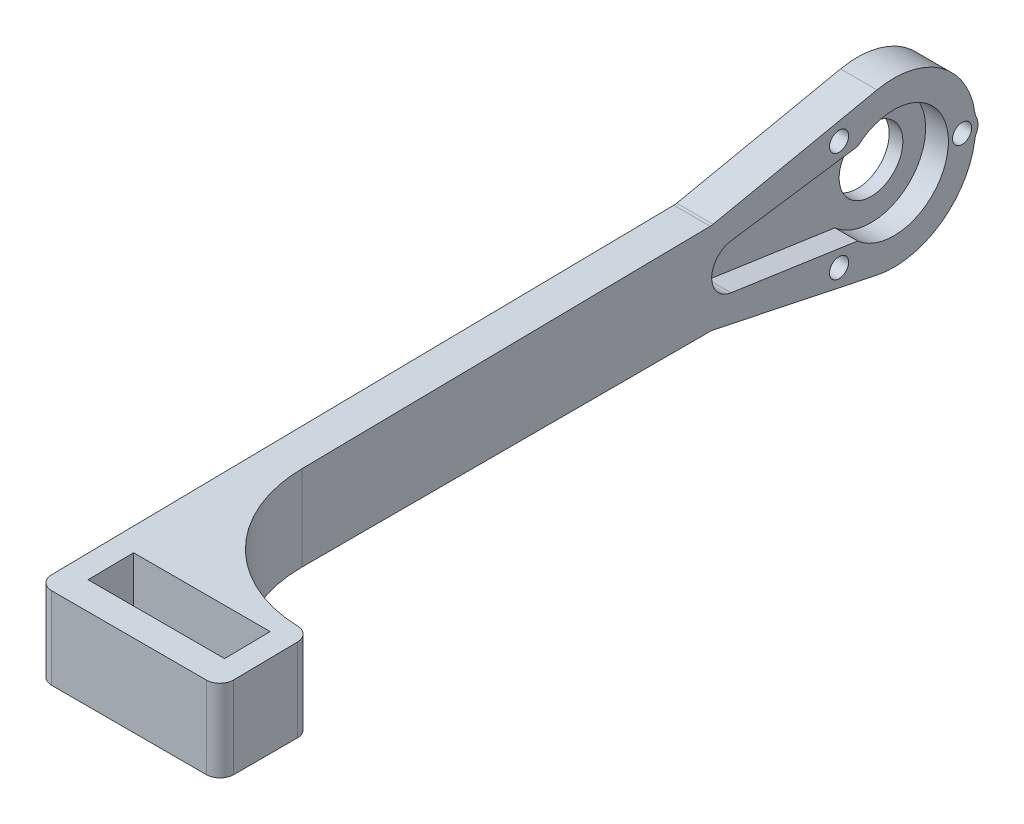
SolidWorks part; units mm, degrees
ref_plane "Plan de face" through (0, 0, 0) normal (0, 0, 1) x (1, 0, 0)
ref_plane "Plan de dessus" through (0, 0, 0) normal (0, 1, 0) x (1, 0, 0)
ref_plane "Plan de droite" through (0, 0, 0) normal (1, 0, 0) x (0, 0, -1)
sketch "Esquisse1" plane through (0, 0, 0) normal (1, 0, 0) x (0, 0, -1)
  line L0 (-47.7273, 0) -> (57.7273, 0) construction
  line L1 (-30, 5) -> (-30, -5)
  line L4 (0, 18.828) -> (0, -23.0645) construction
  line L7 (-30, 5) -> (30, 5)
  line L8 (-30, -5) -> (30, -5)
  line L9 (30, 12.9505) -> (30, -16.4973) construction
  line L10 (48.1521, 8.8082) -> (48.1521, -18.9143) construction
  line L11 (30, 5) -> (48.1521, 8.8082)
  line L12 (30, -5) -> (48.1521, -8.8082)
  line L13 (50, 0) -> (50, 9) construction
  circle A2 centre (-40, 0) radius 11.1803 construction
  arc A5 (48.1521, 8.8082) -> (48.1521, -8.8082) centre (50, 0) cw construction
  arc A8 (48.1521, -8.8082) -> (58.9458, -0.9859) centre (50, 0) ccw
  arc A9 (48.1521, 8.8082) -> (58.9458, 0.9859) centre (50, 0) cw
  circle A10 centre (57.5, 0) radius 1.75 construction
  arc A11 (58.9458, 0.9859) -> (58.9458, -0.9859) centre (57.5, 0) cw
  point P20 (0, -5)
  point P22 (0, 5)
  dimension "D3" = 10
  dimension "D4" = 9
  dimension "D6" = 3.5
  dimension "D5" = 7.5
  dimension "D7" = 40
  dimension "D1" = 80
  dimension "D2" = 90
  dimension "D8" = 20
extrude "Boss.-Extru.1" add sketch "Esquisse1" along normal blind 4 contours L1 | L1 L8 L12 A8 A11 A9 L11 L7 region at (0, 0, -18.2864)
sketch "Esquisse2" plane through (4, 0, 0) normal (1, 0, 0) x (0, 0, -1)
  line L2 (48.1521, 8.8082) -> (30, 5)
  line L8 (30, 5) -> (-30, 5)
  line L9 (30, 5) -> (-30, 5)
  line L10 (-30, -5) -> (30, -5)
  line L11 (-30, -5) -> (30, -5)
  line L14 (48.1521, 8.8082) -> (30, 5)
  line L16 (30, -5) -> (48.1521, -8.8082)
  line L17 (30, -5) -> (48.1521, -8.8082)
  line L19 (-30, 5) -> (-30, -5)
  line L20 (-30, 5) -> (-30, -5)
  arc A2 (58.9458, 0.9859) -> (48.1521, 8.8082) centre (50, 0) ccw
  circle A6 centre (50, 0) radius 3.5
  arc A15 (58.9458, -0.9859) -> (58.9458, 0.9859) centre (57.5, 0) ccw
  arc A17 (58.9458, 0.9859) -> (48.1521, 8.8082) centre (50, 0) ccw
  arc A18 (48.1521, -8.8082) -> (58.9458, -0.9859) centre (50, 0) ccw
  arc A19 (48.1521, -8.8082) -> (58.9458, -0.9859) centre (50, 0) ccw
  arc A21 (58.9458, -0.9859) -> (58.9458, 0.9859) centre (57.5, 0) ccw
  dimension "D3" = 7
  dimension "D1" = 0
extrude "Enlèv. mat.-Extru.1" cut sketch "Esquisse2" against normal blind 10 contours A6
sketch "Esquisse3" plane through (4, 0, 0) normal (1, 0, 0) x (0, 0, -1)
  line L0 (0, 0) -> (74.7488, 0) construction
  line L1 (38.1014, 11.1997) -> (38.1014, -12.7742) construction
  line L2 (48.1521, 8.8082) -> (30, 5)
  line L6 (23.0641, 4.5) -> (53.2637, 4.5) construction
  line L7 (0, 17.2639) -> (0, -16.0675) construction
  line L8 (30.5083, 6.6344) -> (30.5083, -6.2819) construction
  line L9 (32.1392, 2.4738) -> (46.0314, 4.5)
  line L10 (32.1392, -2.4738) -> (46.0314, -4.5)
  line L15 (30, 5) -> (-30, 5)
  line L16 (30, 5) -> (-30, 5)
  line L17 (-30, -5) -> (30, -5)
  line L18 (-30, -5) -> (30, -5)
  line L21 (48.1521, 8.8082) -> (30, 5)
  line L23 (30, -5) -> (48.1521, -8.8082)
  line L24 (30, -5) -> (48.1521, -8.8082)
  line L26 (-30, 5) -> (-30, -5)
  line L27 (-30, 5) -> (-30, -5)
  circle A0 centre (50, 0) radius 6 construction
  circle A1 centre (32.5, 0) radius 2.5 construction
  arc A2 (58.9458, 0.9859) -> (48.1521, 8.8082) centre (50, 0) ccw
  arc A6 (32.1392, -2.4738) -> (32.1392, 2.4738) centre (32.5, 0) cw
  arc A7 (46.0314, -4.5) -> (46.0314, 4.5) centre (50, 0) ccw
  arc A16 (58.9458, -0.9859) -> (58.9458, 0.9859) centre (57.5, 0) ccw
  arc A18 (58.9458, 0.9859) -> (48.1521, 8.8082) centre (50, 0) ccw
  arc A19 (48.1521, -8.8082) -> (58.9458, -0.9859) centre (50, 0) ccw
  arc A20 (48.1521, -8.8082) -> (58.9458, -0.9859) centre (50, 0) ccw
  arc A22 (58.9458, -0.9859) -> (58.9458, 0.9859) centre (57.5, 0) ccw
  dimension "D2" = 12
  dimension "D4" = 17.5
  dimension "D5" = 5
  dimension "D3" = 4.5
  dimension "D1" = 0
extrude "Enlèv. mat.-Extru.2" cut sketch "Esquisse3" against normal blind 2.5 contours A7 L9 A6 L10
sketch "Esquisse5" plane through (4, 0, 0) normal (1, 0, 0) x (0, 0, -1)
  line L0 (0, 16.8077) -> (0, -27.9422) construction
  line L1 (-64.0496, 0) -> (62.7771, 0) construction
  line L2 (32.1392, -2.4738) -> (46.0314, -4.5)
  line L3 (46.0314, 4.5) -> (32.1392, 2.4738)
  line L4 (32.1392, -2.4738) -> (46.0314, -4.5)
  line L5 (46.0314, 4.5) -> (32.1392, 2.4738)
  line L6 (50, 0) -> (34.0152, 15.9848) construction
  line L8 (48.1521, 8.8082) -> (30, 5)
  line L9 (30, 5) -> (-30, 5)
  line L10 (-30, -5) -> (30, -5)
  line L13 (30, 5) -> (-30, 5)
  line L14 (-30, -5) -> (30, -5)
  line L18 (48.1521, 8.8082) -> (30, 5)
  line L20 (30, -5) -> (48.1521, -8.8082)
  line L21 (30, -5) -> (48.1521, -8.8082)
  line L24 (-30, 5) -> (-30, -5)
  line L25 (-30, 5) -> (-30, -5)
  arc A2 (46.0314, -4.5) -> (46.0314, 4.5) centre (50, 0) ccw
  arc A3 (32.1392, 2.4738) -> (32.1392, -2.4738) centre (32.5, 0) ccw
  arc A4 (46.0314, -4.5) -> (46.0314, 4.5) centre (50, 0) ccw
  arc A5 (32.1392, 2.4738) -> (32.1392, -2.4738) centre (32.5, 0) ccw
  arc A6 (58.9458, 0.9859) -> (48.1521, 8.8082) centre (50, 0) ccw
  circle A10 centre (50, 0) radius 8.5 construction
  circle A11 centre (43.9896, 6.0104) radius 1.05
  circle A12 centre (43.9896, -6.0104) radius 1.05
  circle A13 centre (57.5, 0) radius 1.05
  arc A17 (58.9458, -0.9859) -> (58.9458, 0.9859) centre (57.5, 0) ccw
  arc A22 (58.9458, 0.9859) -> (48.1521, 8.8082) centre (50, 0) ccw
  arc A23 (48.1521, -8.8082) -> (58.9458, -0.9859) centre (50, 0) ccw
  arc A24 (48.1521, -8.8082) -> (58.9458, -0.9859) centre (50, 0) ccw
  arc A26 (58.9458, -0.9859) -> (58.9458, 0.9859) centre (57.5, 0) ccw
  dimension "D3" = 2.1
  dimension "D4" = 17
  dimension "D5" = 45
  dimension "D1" = 0
  dimension "D2" = 0
extrude "Enlèv. mat.-Extru.3" cut sketch "Esquisse5" against normal through all contours A11 | A12 | A13
sketch "Esquisse6" plane through (0, 0, 30) normal (0, 0, 1) x (1, 0, 0)
  line L0 (2, 5) -> (2, -5) construction
  line L1 (0, 5) -> (0, -5)
  line L4 (0, 5) -> (0, -5)
  line L5 (0, -5) -> (4, -5)
  line L6 (4, -5) -> (4, 5)
  line L7 (4, 5) -> (0, 5)
  line L9 (0, -5) -> (4, -5)
  line L10 (4, -5) -> (4, 5)
  line L11 (4, 5) -> (0, 5)
  line L12 (20, -5) -> (4, -5)
  line L13 (20, 5) -> (20, -5)
  line L14 (4, 5) -> (20, 5)
  point P3 (20, 0)
  point P7 (20, 8.3224)
  line M9 (0, 5) -> (0, -5)
  line M10 (0, -5) -> (4, -5)
  line M11 (4, -5) -> (4, 5)
  line M12 (4, 5) -> (0, 5)
  dimension "D2" = 18
  dimension "D1" = 0
extrude "Boss.-Extru.2" add sketch "Esquisse6" along normal blind 10 contours L14 L12 L13 M11 | L0 L9 M12 M11 | L0 L11 M9 M10 | M9 region at (3, 0, 30) region at (1, 0, 30) region at (12, 0, 30)
sketch "Esquisse7" plane through (0, 5, 0) normal (0, 1, 0) x (1, 0, 0)
  line L0 (10, -40) -> (10, -30) construction
  line L1 (17.5, -37) -> (2.5, -37)
  line L2 (17.5, -37) -> (17.5, -32)
  line L3 (17.5, -32) -> (2.5, -32)
  line L4 (2.5, -37) -> (2.5, -32)
  line L5 (17.5, -37) -> (2.5, -32) construction
  line L6 (17.5, -32) -> (2.5, -37) construction
  line L8 (4, -30) -> (4, 30)
  line L9 (4, 30) -> (0, 30)
  line L10 (0, 30) -> (0, -40)
  line L11 (0, -40) -> (20, -40)
  line L12 (0, -40) -> (20, -40)
  line L13 (20, -40) -> (20, -30)
  line L14 (20, -40) -> (20, -30)
  line L15 (20, -30) -> (4, -30)
  line L16 (4, -30) -> (4, 30)
  line L18 (0, 30) -> (0, -40)
  line L29 (20, -30) -> (4, -30)
  line L32 (4, 30) -> (0, 30)
  point P2 (10, -34.5)
  dimension "D2" = 15
  dimension "D3" = 5
  dimension "D4" = 2
  dimension "D1" = 0
extrude "Enlèv. mat.-Extru.4" cut sketch "Esquisse7" against normal blind 10 contours L2 L1 L4 L3
fillet "Congé2" radius 1.5 7 edges at (2, 0.9859, -58.9458) (2, -0.9859, -58.9458) (2, 5, -30) (2, -5, -30) (20, 0, 30) (20, 0, 40) (0, 0, 40)
fillet "Congé3" radius 15 1 edges at (4, 0, 30)
sketch "Esquisse8" plane through (20, 0, 0) normal (1, 0, 0) x (0, 0, -1)
  line L0 (-40, 5) -> (-40, 4)
  line L1 (-40, 4) -> (29.8443, 5)
  line L2 (29.8443, 5) -> (-39.25, 5)
  line L3 (-38.5, 5) -> (-40, 5) construction
  line L4 (-38.5, 5) -> (-40, 5)
  line L5 (-40, 5) -> (-40, -5)
  line L6 (-40, -5) -> (-38.5, -5)
  line L7 (-38.5, -5) -> (-38.5, 5)
  line L8 (-38.5, 5) -> (-40, 5) construction
  line L9 (-40, 5) -> (-40, -5) construction
  line L10 (-40, -5) -> (-38.5, -5) construction
  line L11 (-38.5, -5) -> (-38.5, 5) construction
  line L12 (-38.5, -5) -> (-31.5, -5)
  line L13 (-31.5, -5) -> (-31.5, 5)
  line L14 (-31.5, 5) -> (-38.5, 5)
  line L15 (-38.5, 5) -> (-38.5, -5)
  line L16 (-38.5, -5) -> (-31.5, -5) construction
  line L17 (-31.5, -5) -> (-31.5, 5) construction
  line L18 (-31.5, 5) -> (-38.5, 5) construction
  line L19 (-38.5, 5) -> (-38.5, -5) construction
  line L20 (-31.5, -5) -> (-30.0007, -5)
  line L21 (-30.0007, -5) -> (-30.0007, 5)
  line L22 (-30.0007, 5) -> (-31.5, 5)
  line L23 (-31.5, 5) -> (-31.5, -5)
  line L24 (-31.5, -5) -> (-30.0007, -5) construction
  line L25 (-30.0007, -5) -> (-30.0007, 5) construction
  line L26 (-30.0007, 5) -> (-31.5, 5) construction
  line L27 (-31.5, 5) -> (-31.5, -5) construction
  line L28 (-15.0076, 5) -> (-30.0007, 5)
  line L29 (-30.0007, 5) -> (-30.0007, -5)
  line L30 (-30.0007, -5) -> (-15.0076, -5)
  line L31 (-15.0076, -5) -> (-15.0076, 5)
  line L32 (-15.0076, 5) -> (-30.0007, 5) construction
  line L33 (-30.0007, 5) -> (-30.0007, -5) construction
  line L34 (-30.0007, -5) -> (-15.0076, -5) construction
  line L35 (-15.0076, -5) -> (-15.0076, 5) construction
  line L36 (-39.25, 5) -> (-40, 5)
  line L37 (29.8443, 5) -> (-15.0076, 5)
  line L38 (-15.0076, 5) -> (-15.0076, -5)
  line L39 (-15.0076, -5) -> (29.8443, -5)
  line L40 (30.1523, -5.032) -> (48.1521, -8.8082)
  line L41 (48.1521, 8.8082) -> (30.1523, 5.032)
  line L42 (29.8443, 5) -> (-15.0076, 5) construction
  line L43 (-15.0076, 5) -> (-15.0076, -5) construction
  line L44 (-15.0076, -5) -> (29.8443, -5) construction
  line L45 (30.1523, -5.032) -> (48.1521, -8.8082) construction
  line L46 (48.1521, 8.8082) -> (30.1523, 5.032) construction
  line L47 (11, 0) -> (-11, 0) construction
  line L48 (29.8443, -5) -> (-39.25, -5)
  line L49 (-40, -4) -> (29.8443, -5)
  line L50 (-40, -5) -> (-40, -4)
  line L51 (-39.25, -5) -> (-40, -5)
  arc A7 (30.1523, -5.032) -> (29.8443, -5) centre (29.8443, -6.5) ccw
  arc A8 (48.1521, -8.8082) -> (58.9107, -1.2646) centre (50, 0) ccw
  arc A9 (59.0593, -0.7944) -> (58.9107, -1.2646) centre (60.3958, -1.4753) ccw
  arc A10 (59.0593, -0.7944) -> (59.0593, 0.7944) centre (57.5, 0) ccw
  arc A11 (58.9107, 1.2646) -> (59.0593, 0.7944) centre (60.3958, 1.4753) ccw
  arc A12 (58.9107, 1.2646) -> (48.1521, 8.8082) centre (50, 0) ccw
  arc A13 (29.8443, 5) -> (30.1523, 5.032) centre (29.8443, 6.5) ccw
  arc A14 (30.1523, -5.032) -> (29.8443, -5) centre (29.8443, -6.5) ccw construction
  arc A15 (48.1521, -8.8082) -> (58.9107, -1.2646) centre (50, 0) ccw construction
  arc A16 (59.0593, -0.7944) -> (58.9107, -1.2646) centre (60.3958, -1.4753) ccw construction
  arc A17 (59.0593, -0.7944) -> (59.0593, 0.7944) centre (57.5, 0) ccw construction
  arc A18 (58.9107, 1.2646) -> (59.0593, 0.7944) centre (60.3958, 1.4753) ccw construction
  arc A19 (58.9107, 1.2646) -> (48.1521, 8.8082) centre (50, 0) ccw construction
  arc A20 (29.8443, 5) -> (30.1523, 5.032) centre (29.8443, 6.5) ccw construction
  point P33 (29.3226, 5)
  line M33 (-31.5, -5) -> (-31.5, 5)
  line M34 (-31.5, 5) -> (-38.5, 5)
  line M35 (-38.5, 5) -> (-38.5, -5)
  dimension "D6" = 8
  dimension "D1" = 0
  dimension "D2" = 0
  dimension "D3" = 0
  dimension "D4" = 0
  dimension "D5" = 0
extrude "Enlèv. mat.-Extru.5" cut sketch "Esquisse8" against normal through all and the other way through all contours L1 L2 M33 | L1 M35 M33 M34 | L36 L0 L1 L2 region at (20, 4.5353, 35.063) region at (20, 4.5662, 30.7534)
